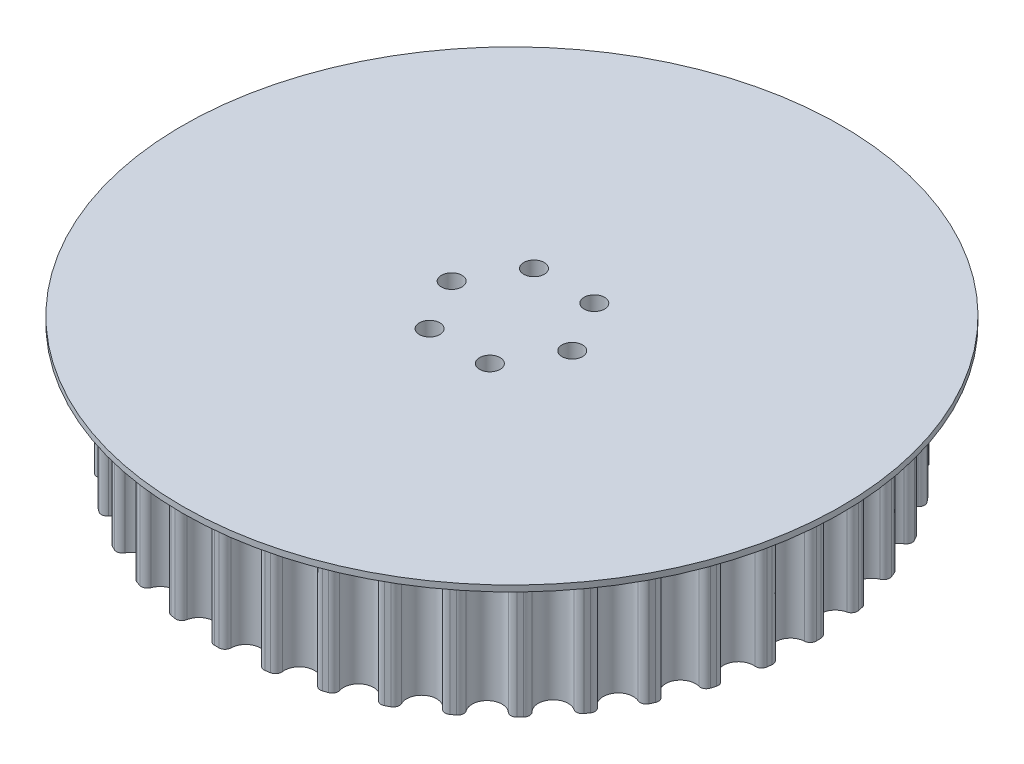
SolidWorks part; units mm, degrees
material "PETG"
ref_plane "Front Plane" through (0, 0, 0) normal (0, 0, 1) x (1, 0, 0)
ref_plane "Top Plane" through (0, 0, 0) normal (0, 1, 0) x (1, 0, 0)
ref_plane "Right Plane" through (0, 0, 0) normal (1, 0, 0) x (0, 0, -1)
sketch "Sketch5" plane through (0, 0, 0) normal (0, 1, 0) x (1, 0, 0)
  line L0 (0, 9.7022) -> (0, 50009.7022) construction
  line L1 (0, 0) -> (0, 48.1826) construction
  line L3 (0, 0) -> (-3.9957, 49.4953) construction
  line L5 (0, 0) -> (3.9957, 49.4953) construction
  circle A0 centre (0, 0) radius 49.6563 construction
  circle A2 centre (0, 0) radius 48.97 construction
  arc A3 (-2.4775, 47.9411) -> (2.4775, 47.9411) centre (0, 48.1826) ccw
  arc A43 (3.9404, 48.8112) -> (3.5451, 48.8415) centre (0, 0) ccw
  arc A45 (-3.5451, 48.8415) -> (-3.9404, 48.8112) centre (0, 0) ccw
  arc A46 (-2.4775, 47.9411) -> (-3.5451, 48.8415) centre (-3.4727, 47.8441) ccw
  arc A47 (3.5451, 48.8415) -> (2.4775, 47.9411) centre (3.4727, 47.8441) ccw
  arc A48 (5.2449, 47.7177) -> (10.1357, 46.9229) centre (7.729, 47.5586) ccw
  arc A49 (5.2449, 47.7177) -> (4.3355, 48.7777) centre (4.247, 47.7816) ccw
  arc A50 (4.3355, 48.7777) -> (3.9404, 48.8112) centre (0, 0) ccw
  arc A51 (11.334, 47.6403) -> (10.1357, 46.9229) centre (11.1025, 46.6675) ccw
  arc A52 (11.7193, 47.547) -> (11.334, 47.6403) centre (0, 0) ccw
  arc A53 (12.8315, 46.2584) -> (17.5314, 44.6894) centre (15.2579, 45.703) ccw
  arc A54 (12.8315, 46.2584) -> (12.1038, 47.4506) centre (11.8567, 46.4816) ccw
  arc A55 (12.1038, 47.4506) -> (11.7193, 47.547) centre (0, 0) ccw
  arc A56 (18.8292, 45.2053) -> (17.5314, 44.6894) centre (18.4447, 44.2822) ccw
  arc A57 (19.1946, 45.0514) -> (18.8292, 45.2053) centre (0, 0) ccw
  arc A58 (20.0857, 43.6011) -> (24.473, 41.2984) centre (22.3916, 42.6636) ccw
  arc A59 (20.0857, 43.6011) -> (19.5587, 44.8945) centre (19.1593, 43.9777) ccw
  arc A60 (19.5587, 44.8945) -> (19.1946, 45.0514) centre (0, 0) ccw
  arc A61 (25.8368, 41.5995) -> (24.473, 41.2984) centre (25.3092, 40.75) ccw
  arc A62 (26.1728, 41.389) -> (25.8368, 41.5995) centre (0, 0) ccw
  arc A63 (26.8197, 39.8145) -> (30.7809, 36.8379) centre (28.9453, 38.5192) ccw
  arc A64 (26.8197, 39.8145) -> (26.507, 41.1757) centre (25.9657, 40.3349) ccw
  arc A65 (26.507, 41.1757) -> (26.1728, 41.389) centre (0, 0) ccw
  arc A66 (32.1753, 36.9163) -> (30.7809, 36.8379) centre (31.5183, 36.1624) ccw
  arc A67 (32.4731, 36.6546) -> (32.1753, 36.9163) centre (0, 0) ccw
  arc A68 (32.8591, 34.9967) -> (36.2915, 31.4232) centre (34.7494, 33.3773) ccw
  arc A69 (32.8591, 34.9967) -> (32.7688, 36.3905) centre (32.0997, 35.6473) ccw
  arc A70 (32.7688, 36.3905) -> (32.4731, 36.6546) centre (0, 0) ccw
  arc A71 (37.6804, 31.2769) -> (36.2915, 31.4232) centre (36.911, 30.6382) ccw
  arc A72 (37.9324, 30.9709) -> (37.6804, 31.2769) centre (0, 0) ccw
  arc A73 (38.0474, 29.2726) -> (40.8621, 25.1948) centre (39.6535, 27.3708) ccw
  arc A74 (38.0474, 29.2726) -> (38.1819, 30.6627) centre (37.4022, 30.0366) ccw
  arc A75 (38.1819, 30.6627) -> (37.9324, 30.9709) centre (0, 0) ccw
  arc A76 (42.2096, 24.8275) -> (40.8621, 25.1948) centre (41.3477, 24.3206) ccw
  arc A77 (42.4093, 24.485) -> (42.2096, 24.8275) centre (0, 0) ccw
  arc A78 (42.2504, 22.7903) -> (44.3745, 18.3137) centre (43.5306, 20.6555) ccw
  arc A79 (42.2504, 22.7903) -> (42.6061, 24.1408) centre (41.7361, 23.6479) ccw
  arc A80 (42.6061, 24.1408) -> (42.4093, 24.485) centre (0, 0) ccw
  arc A81 (45.6457, 17.7351) -> (44.3745, 18.3137) centre (44.7135, 17.373) ccw
  arc A82 (45.7877, 17.365) -> (45.6457, 17.7351) centre (0, 0) ccw
  arc A83 (45.3591, 15.7177) -> (46.7376, 10.9584) centre (46.2803, 13.4052) ccw
  arc A84 (45.3591, 15.7177) -> (45.9268, 16.9937) centre (44.989, 16.6467) ccw
  arc A85 (45.9268, 16.9937) -> (45.7877, 17.365) centre (0, 0) ccw
  arc A86 (47.8995, 10.1834) -> (46.7376, 10.9584) centre (46.9213, 9.9754) ccw
  arc A87 (47.9803, 9.7953) -> (47.8995, 10.1834) centre (0, 0) ccw
  arc A88 (47.293, 8.2381) -> (47.8902, 3.3193) centre (47.8313, 5.8078) ccw
  arc A89 (47.293, 8.2381) -> (48.0581, 9.4065) centre (47.0767, 9.2144) ccw
  arc A90 (48.0581, 9.4065) -> (47.9803, 9.7953) centre (0, 0) ccw
  arc A91 (48.9127, 2.3679) -> (47.8902, 3.3193) centre (47.9139, 2.3195) ccw
  arc A92 (48.9303, 1.9718) -> (48.9127, 2.3679) centre (0, 0) ccw
  arc A93 (48.002, 0.5451) -> (47.8025, -4.4058) centre (48.1435, -1.9401) ccw
  arc A94 (48.002, 0.5451) -> (48.9446, 1.5756) centre (47.9452, 1.5434) ccw
  arc A95 (48.9446, 1.5756) -> (48.9303, 1.9718) centre (0, 0) ccw
  arc A96 (48.6591, -5.5089) -> (47.8025, -4.4058) centre (47.6655, -5.3964) ccw
  arc A97 (48.613, -5.9027) -> (48.6591, -5.5089) centre (0, 0) ccw
  arc A98 (47.4678, -7.1621) -> (46.4767, -12.0169) centre (47.2089, -9.6378) ccw
  arc A99 (47.4678, -7.1621) -> (48.5636, -6.2961) centre (47.5719, -6.1675) ccw
  arc A100 (48.5636, -6.2961) -> (48.613, -5.9027) centre (0, 0) ccw
  arc A101 (47.1453, -13.2431) -> (46.4767, -12.0169) centre (46.1826, -12.9726) ccw
  arc A102 (47.0366, -13.6243) -> (47.1453, -13.2431) centre (0, 0) ccw
  arc A103 (45.7043, -14.6837) -> (43.9472, -19.3166) centre (45.0515, -17.0858) ccw
  arc A104 (45.7043, -14.6837) -> (46.9247, -14.0047) centre (45.9665, -13.7187) ccw
  arc A105 (46.9247, -14.0047) -> (47.0366, -13.6243) centre (0, 0) ccw
  arc A106 (44.4105, -20.6342) -> (43.9472, -19.3166) centre (43.5036, -20.2128) ccw
  arc A107 (44.242, -20.9931) -> (44.4105, -20.6342) centre (0, 0) ccw
  arc A108 (42.757, -21.825) -> (40.2795, -26.1161) centre (41.7274, -24.0913) ccw
  arc A109 (42.757, -21.825) -> (44.0706, -21.3506) centre (43.1706, -20.9146) ccw
  arc A110 (44.0706, -21.3506) -> (44.242, -20.9931) centre (0, 0) ccw
  arc A111 (40.5254, -27.4909) -> (40.2795, -26.1161) centre (39.6979, -26.9296) ccw
  arc A112 (40.3015, -27.8181) -> (40.5254, -27.4909) centre (0, 0) ccw
  arc A113 (38.7023, -28.4011) -> (35.5686, -32.2392) centre (37.3225, -30.4729) ccw
  arc A114 (38.7023, -28.4011) -> (40.075, -28.1435) centre (39.2566, -27.5688) ccw
  arc A115 (40.075, -28.1435) -> (40.3015, -27.8181) centre (0, 0) ccw
  arc A116 (35.5908, -33.6357) -> (35.5686, -32.2392) centre (34.864, -32.9488) ccw
  arc A117 (35.3173, -33.9227) -> (35.5908, -33.6357) centre (0, 0) ccw
  arc A118 (33.6453, -34.2416) -> (29.9364, -37.5273) centre (31.951, -36.0652) ccw
  arc A119 (33.6453, -34.2416) -> (35.0415, -34.2075) centre (34.3259, -33.509) ccw
  arc A120 (35.0415, -34.2075) -> (35.3173, -33.9227) centre (0, 0) ccw
  arc A121 (29.7343, -38.9093) -> (29.9364, -37.5273) centre (29.1271, -38.1147) ccw
  arc A122 (29.4183, -39.1487) -> (29.7343, -38.9093) centre (0, 0) ccw
  arc A123 (27.7168, -39.1953) -> (23.529, -41.8435) centre (25.752, -40.7235) ccw
  arc A124 (27.7168, -39.1953) -> (29.1004, -39.3856) centre (28.5062, -38.5813) ccw
  arc A125 (29.1004, -39.3856) -> (29.4183, -39.1487) centre (0, 0) ccw
  arc A126 (23.1078, -43.1751) -> (23.529, -41.8435) centre (22.6359, -42.2934) ccw
  arc A127 (22.7575, -43.3608) -> (23.1078, -43.1751) centre (0, 0) ccw
  arc A128 (21.0705, -43.1338) -> (16.5121, -45.0759) centre (18.886, -44.327) ccw
  arc A129 (21.0705, -43.1338) -> (22.4057, -43.5436) centre (21.9482, -42.6544) ccw
  arc A130 (22.4057, -43.5436) -> (22.7575, -43.3608) centre (0, 0) ccw
  arc A131 (15.8828, -46.3228) -> (16.5121, -45.0759) centre (15.5584, -45.3768) ccw
  arc A132 (15.5072, -46.4498) -> (15.8828, -46.3228) centre (0, 0) ccw
  arc A133 (13.8785, -45.9552) -> (9.0676, -47.1409) centre (11.5309, -46.7825) ccw
  arc A134 (13.8785, -45.9552) -> (15.1307, -46.5739) centre (14.8217, -45.6228) ccw
  arc A135 (15.1307, -46.5739) -> (15.5072, -46.4498) centre (0, 0) ccw
  arc A136 (8.2464, -48.2707) -> (9.0676, -47.1409) centre (8.078, -47.285) ccw
  arc A137 (7.8553, -48.3359) -> (8.2464, -48.2707) centre (0, 0) ccw
  arc A138 (6.3271, -47.5863) -> (1.3882, -47.985) centre (3.8771, -48.0264) ccw
  arc A139 (6.3271, -47.5863) -> (7.4638, -48.3979) centre (7.3113, -47.4095) ccw
  arc A140 (7.4638, -48.3979) -> (7.8553, -48.3359) centre (0, 0) ccw
  arc A141 (0.3965, -48.9684) -> (1.3882, -47.985) centre (0.3884, -47.9684) ccw
  arc A142 (0, -48.97) -> (0.3965, -48.9684) centre (0, 0) ccw
  arc A143 (-1.3882, -47.985) -> (-6.3271, -47.5863) centre (-3.8771, -48.0264) ccw
  arc A144 (-1.3882, -47.985) -> (-0.3965, -48.9684) centre (-0.3884, -47.9684) ccw
  arc A145 (-0.3965, -48.9684) -> (0, -48.97) centre (0, 0) ccw
  arc A146 (-7.4638, -48.3979) -> (-6.3271, -47.5863) centre (-7.3113, -47.4095) ccw
  arc A147 (-7.8553, -48.3359) -> (-7.4638, -48.3979) centre (0, 0) ccw
  arc A148 (-9.0676, -47.1409) -> (-13.8785, -45.9552) centre (-11.5309, -46.7825) ccw
  arc A149 (-9.0676, -47.1409) -> (-8.2464, -48.2707) centre (-8.078, -47.285) ccw
  arc A150 (-8.2464, -48.2707) -> (-7.8553, -48.3359) centre (0, 0) ccw
  arc A151 (-15.1307, -46.5739) -> (-13.8785, -45.9552) centre (-14.8217, -45.6228) ccw
  arc A152 (-15.5072, -46.4498) -> (-15.1307, -46.5739) centre (0, 0) ccw
  arc A153 (-16.5121, -45.0759) -> (-21.0705, -43.1338) centre (-18.886, -44.327) ccw
  arc A154 (-16.5121, -45.0759) -> (-15.8828, -46.3228) centre (-15.5584, -45.3768) ccw
  arc A155 (-15.8828, -46.3228) -> (-15.5072, -46.4498) centre (0, 0) ccw
  arc A156 (-22.4057, -43.5436) -> (-21.0705, -43.1338) centre (-21.9482, -42.6544) ccw
  arc A157 (-22.7575, -43.3608) -> (-22.4057, -43.5436) centre (0, 0) ccw
  arc A158 (-23.529, -41.8435) -> (-27.7168, -39.1953) centre (-25.752, -40.7235) ccw
  arc A159 (-23.529, -41.8435) -> (-23.1078, -43.1751) centre (-22.6359, -42.2934) ccw
  arc A160 (-23.1078, -43.1751) -> (-22.7575, -43.3608) centre (0, 0) ccw
  arc A161 (-29.1004, -39.3856) -> (-27.7168, -39.1953) centre (-28.5062, -38.5813) ccw
  arc A162 (-29.4183, -39.1487) -> (-29.1004, -39.3856) centre (0, 0) ccw
  arc A163 (-29.9364, -37.5273) -> (-33.6453, -34.2416) centre (-31.951, -36.0652) ccw
  arc A164 (-29.9364, -37.5273) -> (-29.7343, -38.9093) centre (-29.1271, -38.1147) ccw
  arc A165 (-29.7343, -38.9093) -> (-29.4183, -39.1487) centre (0, 0) ccw
  arc A166 (-35.0415, -34.2075) -> (-33.6453, -34.2416) centre (-34.3259, -33.509) ccw
  arc A167 (-35.3173, -33.9227) -> (-35.0415, -34.2075) centre (0, 0) ccw
  arc A168 (-35.5686, -32.2392) -> (-38.7023, -28.4011) centre (-37.3225, -30.4729) ccw
  arc A169 (-35.5686, -32.2392) -> (-35.5908, -33.6357) centre (-34.864, -32.9488) ccw
  arc A170 (-35.5908, -33.6357) -> (-35.3173, -33.9227) centre (0, 0) ccw
  arc A171 (-40.075, -28.1435) -> (-38.7023, -28.4011) centre (-39.2566, -27.5688) ccw
  arc A172 (-40.3015, -27.8181) -> (-40.075, -28.1435) centre (0, 0) ccw
  arc A173 (-40.2795, -26.1161) -> (-42.757, -21.825) centre (-41.7274, -24.0913) ccw
  arc A174 (-40.2795, -26.1161) -> (-40.5254, -27.4909) centre (-39.6979, -26.9296) ccw
  arc A175 (-40.5254, -27.4909) -> (-40.3015, -27.8181) centre (0, 0) ccw
  arc A176 (-44.0706, -21.3506) -> (-42.757, -21.825) centre (-43.1706, -20.9146) ccw
  arc A177 (-44.242, -20.9931) -> (-44.0706, -21.3506) centre (0, 0) ccw
  arc A178 (-43.9472, -19.3166) -> (-45.7043, -14.6837) centre (-45.0515, -17.0858) ccw
  arc A179 (-43.9472, -19.3166) -> (-44.4105, -20.6342) centre (-43.5036, -20.2128) ccw
  arc A180 (-44.4105, -20.6342) -> (-44.242, -20.9931) centre (0, 0) ccw
  arc A181 (-46.9247, -14.0047) -> (-45.7043, -14.6837) centre (-45.9665, -13.7187) ccw
  arc A182 (-47.0366, -13.6243) -> (-46.9247, -14.0047) centre (0, 0) ccw
  arc A183 (-46.4767, -12.0169) -> (-47.4678, -7.1621) centre (-47.2089, -9.6378) ccw
  arc A184 (-46.4767, -12.0169) -> (-47.1453, -13.2431) centre (-46.1826, -12.9726) ccw
  arc A185 (-47.1453, -13.2431) -> (-47.0366, -13.6243) centre (0, 0) ccw
  arc A186 (-48.5636, -6.2961) -> (-47.4678, -7.1621) centre (-47.5719, -6.1675) ccw
  arc A187 (-48.613, -5.9027) -> (-48.5636, -6.2961) centre (0, 0) ccw
  arc A188 (-47.8025, -4.4058) -> (-48.002, 0.5451) centre (-48.1435, -1.9401) ccw
  arc A189 (-47.8025, -4.4058) -> (-48.6591, -5.5089) centre (-47.6655, -5.3964) ccw
  arc A190 (-48.6591, -5.5089) -> (-48.613, -5.9027) centre (0, 0) ccw
  arc A191 (-48.9446, 1.5756) -> (-48.002, 0.5451) centre (-47.9452, 1.5434) ccw
  arc A192 (-48.9303, 1.9718) -> (-48.9446, 1.5756) centre (0, 0) ccw
  arc A193 (-47.8902, 3.3193) -> (-47.293, 8.2381) centre (-47.8313, 5.8078) ccw
  arc A194 (-47.8902, 3.3193) -> (-48.9127, 2.3679) centre (-47.9139, 2.3195) ccw
  arc A195 (-48.9127, 2.3679) -> (-48.9303, 1.9718) centre (0, 0) ccw
  arc A196 (-48.0581, 9.4065) -> (-47.293, 8.2381) centre (-47.0767, 9.2144) ccw
  arc A197 (-47.9803, 9.7953) -> (-48.0581, 9.4065) centre (0, 0) ccw
  arc A198 (-46.7376, 10.9584) -> (-45.3591, 15.7177) centre (-46.2803, 13.4052) ccw
  arc A199 (-46.7376, 10.9584) -> (-47.8995, 10.1834) centre (-46.9213, 9.9754) ccw
  arc A200 (-47.8995, 10.1834) -> (-47.9803, 9.7953) centre (0, 0) ccw
  arc A201 (-45.9268, 16.9937) -> (-45.3591, 15.7177) centre (-44.989, 16.6467) ccw
  arc A202 (-45.7877, 17.365) -> (-45.9268, 16.9937) centre (0, 0) ccw
  arc A203 (-44.3745, 18.3137) -> (-42.2504, 22.7903) centre (-43.5306, 20.6555) ccw
  arc A204 (-44.3745, 18.3137) -> (-45.6457, 17.7351) centre (-44.7135, 17.373) ccw
  arc A205 (-45.6457, 17.7351) -> (-45.7877, 17.365) centre (0, 0) ccw
  arc A206 (-42.6061, 24.1408) -> (-42.2504, 22.7903) centre (-41.7361, 23.6479) ccw
  arc A207 (-42.4093, 24.485) -> (-42.6061, 24.1408) centre (0, 0) ccw
  arc A208 (-40.8621, 25.1948) -> (-38.0474, 29.2726) centre (-39.6535, 27.3708) ccw
  arc A209 (-40.8621, 25.1948) -> (-42.2096, 24.8275) centre (-41.3477, 24.3206) ccw
  arc A210 (-42.2096, 24.8275) -> (-42.4093, 24.485) centre (0, 0) ccw
  arc A211 (-38.1819, 30.6627) -> (-38.0474, 29.2726) centre (-37.4022, 30.0366) ccw
  arc A212 (-37.9324, 30.9709) -> (-38.1819, 30.6627) centre (0, 0) ccw
  arc A213 (-36.2915, 31.4232) -> (-32.8591, 34.9967) centre (-34.7494, 33.3773) ccw
  arc A214 (-36.2915, 31.4232) -> (-37.6804, 31.2769) centre (-36.911, 30.6382) ccw
  arc A215 (-37.6804, 31.2769) -> (-37.9324, 30.9709) centre (0, 0) ccw
  arc A216 (-32.7688, 36.3905) -> (-32.8591, 34.9967) centre (-32.0997, 35.6473) ccw
  arc A217 (-32.4731, 36.6546) -> (-32.7688, 36.3905) centre (0, 0) ccw
  arc A218 (-30.7809, 36.8379) -> (-26.8197, 39.8145) centre (-28.9453, 38.5192) ccw
  arc A219 (-30.7809, 36.8379) -> (-32.1753, 36.9163) centre (-31.5183, 36.1624) ccw
  arc A220 (-32.1753, 36.9163) -> (-32.4731, 36.6546) centre (0, 0) ccw
  arc A221 (-26.507, 41.1757) -> (-26.8197, 39.8145) centre (-25.9657, 40.3349) ccw
  arc A222 (-26.1728, 41.389) -> (-26.507, 41.1757) centre (0, 0) ccw
  arc A223 (-24.473, 41.2984) -> (-20.0857, 43.6011) centre (-22.3916, 42.6636) ccw
  arc A224 (-24.473, 41.2984) -> (-25.8368, 41.5995) centre (-25.3092, 40.75) ccw
  arc A225 (-25.8368, 41.5995) -> (-26.1728, 41.389) centre (0, 0) ccw
  arc A226 (-19.5587, 44.8945) -> (-20.0857, 43.6011) centre (-19.1593, 43.9777) ccw
  arc A227 (-19.1946, 45.0514) -> (-19.5587, 44.8945) centre (0, 0) ccw
  arc A228 (-17.5314, 44.6894) -> (-12.8315, 46.2584) centre (-15.2579, 45.703) ccw
  arc A229 (-17.5314, 44.6894) -> (-18.8292, 45.2053) centre (-18.4447, 44.2822) ccw
  arc A230 (-18.8292, 45.2053) -> (-19.1946, 45.0514) centre (0, 0) ccw
  arc A231 (-12.1038, 47.4506) -> (-12.8315, 46.2584) centre (-11.8567, 46.4816) ccw
  arc A232 (-11.7193, 47.547) -> (-12.1038, 47.4506) centre (0, 0) ccw
  arc A233 (-10.1357, 46.9229) -> (-5.2449, 47.7177) centre (-7.729, 47.5586) ccw
  arc A234 (-10.1357, 46.9229) -> (-11.334, 47.6403) centre (-11.1025, 46.6675) ccw
  arc A235 (-11.334, 47.6403) -> (-11.7193, 47.547) centre (0, 0) ccw
  arc A236 (-4.3355, 48.7777) -> (-5.2449, 47.7177) centre (-4.247, 47.7816) ccw
  arc A237 (-3.9404, 48.8112) -> (-4.3355, 48.7777) centre (0, 0) ccw
  point P9 (0, 45.6934)
  point P14 (0, 49.6563)
  point P31 (0, 48.97)
  dimension "D3" = 2.4892
  dimension "D4" = 99.3127
  dimension "D6" = 1
  dimension "D2" = 97.94
  dimension "D1" = 3.2766
  dimension "D5" = 8
  dimension "D7" = 39
extrude "Boss-Extrude3" add sketch "Sketch5" along normal mid plane 22 contours A2 | A45 A237 A236 A233 A234 A235 A232 A231 A228 A229 A230 A227 A226 A223 A224 A225 A222 A221 A218 A219 A220 A217 A216 A213 A214 A215 A212 A211 A208 A209 A210 A207 A206 A203 A204 A205 A202 A201 A198 A199 A200 A197 A196 region at (0, 0, 0)
sketch "Sketch2" plane through (0, 11, 0) normal (0, 1, 0) x (1, 0, 0)
  circle A0 centre (0, 0) radius 54.6563
  dimension "D1" = 109.3127
extrude "Boss-Extrude2" add sketch "Sketch2" along normal blind 1
sketch "Sketch3" plane through (0, 12, 0) normal (0, 1, 0) x (1, 0, 0)
  line L0 (0, 0) -> (10, 0) construction
  circle A0 centre (10, 0) radius 1.7
  circle A1 centre (5, -8.6603) radius 1.7
  circle A2 centre (-5, -8.6603) radius 1.7
  circle A3 centre (-10, 0) radius 1.7
  circle A4 centre (-5, 8.6603) radius 1.7
  circle A5 centre (5, 8.6603) radius 1.7
  dimension "D1" = 10
  dimension "D2" = 3.4
  dimension "D3" = 6
extrude "Cut-Extrude1" cut sketch "Sketch3" against normal through all
sketch "Sketch4" plane through (0, -11, 0) normal (0, 1, 0) x (1, 0, 0)
  line L0 (0, 0) -> (5, -8.6603) construction
  circle A0 centre (5, -8.6603) radius 3
  circle A1 centre (-5, -8.6603) radius 3
  circle A2 centre (-10, 0) radius 3
  circle A3 centre (-5, 8.6603) radius 3
  circle A4 centre (5, 8.6603) radius 3
  circle A5 centre (10, 0) radius 3
  dimension "D1" = 6
  dimension "D2" = 6
extrude "Cut-Extrude2" cut sketch "Sketch4" along normal offset from surface (13 mm away) 10 up to face at (10, 12, 1.7)
sketch "Sketch6" plane through (0, -11, 0) normal (0, -1, 0) x (1, 0, 0)
  line L0 (0, 0) -> (35, 0) construction
  circle A0 centre (35, 0) radius 1.985
  circle A1 centre (-17.5, -30.3109) radius 1.985
  circle A2 centre (-17.5, 30.3109) radius 1.985
  dimension "D2" = 3.97
  dimension "D1" = 35
  dimension "D3" = 3
extrude "Cut-Extrude3" cut sketch "Sketch6" against normal blind 20
equation "\"pitch\"= 8mm"
equation "\"n\"= 39"
equation "\"pitch_dia\"= \"pitch\" * \"n\" / PI"
equation "\"outside_dia\"= 97.94'From manual. For 39 teeth"
equation "\"belt_width\"= 22mm"
equation "\"D1@Sketch2\"=\"pitch_dia\"+10.00mm"
equation "\"D4@Sketch5\"=\"pitch_dia\""
equation "\"D1@Boss-Extrude3\" = \"belt_width\""
equation "\"D7@Sketch5\"=\"n\""
equation "\"D5@Sketch5\"=\"pitch\""
equation "\"tol_dia_id_intfc\" = 0.0200mm ' For hole diameters - Interference fit"
equation "\"tol_dia_id_slip\"  = 0.0300mm ' For hole diameters - Slip fit"
equation "\"tol_dia_id_clear\" = 0.0500mm ' For hole diameters - Clearance fit"
equation "\"tol_dia_od_intfc\" = 0.0200mm ' For shaft diameters - Interference fit"
equation "\"tol_dia_od_slip\"  = 0.0300mm ' For shaft diameters - Slip fit"
equation "\"tol_dia_od_clear\" = 0.0500mm ' For shaft diameters - Clearance fit"
equation "\"tol_general_intfc\"= 0.0030mm ' For general parts (Horiz) - Interference fit"
equation "\"tol_general_slip\" = 0.0050mm ' For general parts (Horiz) - Slip fit"
equation "\"tol_general_clear\"= 0.0100mm ' For general parts (Horiz) - Clearance fit"
equation "\"tol_layer_intfc\"  = 0.0030mm ' For all parts (Vert) - Interference fit"
equation "\"tol_layer_slip\"   = 0.0050mm ' For all parts (Vert) - Slip fit"
equation "\"tol_layer_clear\"  = 0.0100mm ' For all parts (Vert) - Clearance fit"
equation "\"tol_corner_rad\"   = 0.100mm ' For corners that fit into other parts"
equation "\"D2@Sketch6\"=3.95+\"tol_dia_id_intfc\""
equation "\"D2@Sketch5\"=\"outside_dia\""
